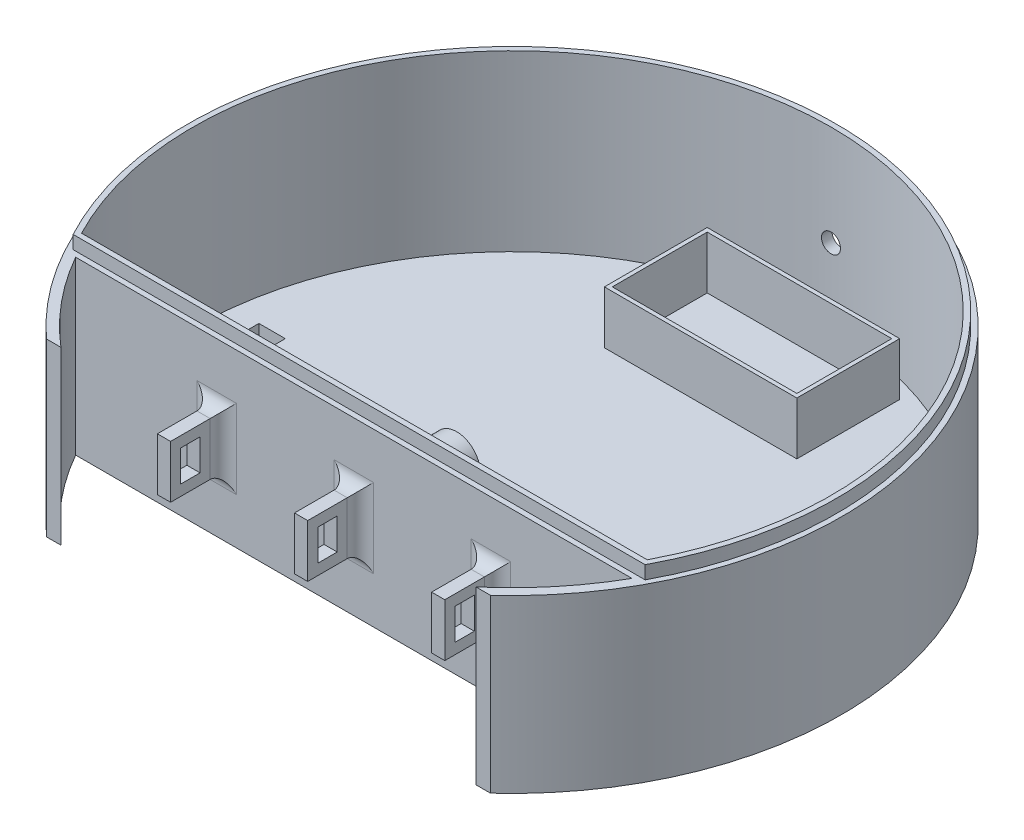
SolidWorks part; units mm, degrees
ref_plane "Plano frontal" through (0, 0, 0) normal (0, 0, 1) x (1, 0, 0)
ref_plane "Plano superior" through (0, 0, 0) normal (0, 1, 0) x (1, 0, 0)
ref_plane "Plano direito" through (0, 0, 0) normal (1, 0, 0) x (0, 0, -1)
sketch "Esboço1" plane through (0, 0, 0) normal (0, 1, 0) x (1, 0, 0)
  line L0 (-109.6586, -60) -> (109.6586, -60)
  circle A0 centre (0, 0) radius 125
  point P5 (0, -125)
  dimension "D1" = 250
  dimension "D2" = 65
extrude "Ressalto-extrusão1" add sketch "Esboço1" along normal blind 70 contours L0 A0 region at (0, 0, -22.5722)
sketch "Esboço5" plane through (0, 70, 0) normal (0, 1, 0) x (1, 0, 0)
  line L1 (-84.2002, -92.3868) -> (-78.7002, -92.3868)
  line L2 (-109.6586, -60) -> (109.6586, -60) construction
  line L3 (78.7002, -92.3868) -> (84.2002, -92.3868)
  line L4 (105.4943, -60) -> (109.6586, -60)
  line L5 (-109.6586, -60) -> (-105.4943, -60)
  arc A0 (-109.6586, -60) -> (-84.2002, -92.3868) centre (0, 0) ccw
  arc A1 (109.6586, -60) -> (84.2002, -92.3868) centre (0, 0) cw
  arc A2 (-105.4943, -60) -> (-78.7002, -92.3868) centre (0, 0) ccw
  arc A3 (78.7002, -92.3868) -> (105.4943, -60) centre (0, 0) ccw
  dimension "D1" = 5.5
  dimension "D2" = 5.5
extrude "Ressalto-extrusão4" add sketch "Esboço5" against normal up to surface (70 mm away) contours A2 L1 A0 L5 | A1 L3 A3 L4 up to face at (0, 0, -32.5)
shell "Casca1" thickness 4 removed face at (0, 70, 45.7497)
sketch "Esboço17" plane through (0, 4, 0) normal (0, 1, 0) x (1, 0, 0)
  line L0 (0, 0) -> (-50000, 0) construction
  line L1 (0, 0) -> (0, 50000) construction
  line L2 (-110, -14) -> (-100, -14)
  line L3 (-110, -14) -> (-110, 14)
  line L4 (-110, 14) -> (-100, 14)
  line L5 (-100, -14) -> (-100, 14)
  line L6 (-110, -14) -> (-100, 14) construction
  line L7 (-110, 14) -> (-100, -14) construction
  line L8 (110, 14) -> (100, -14) construction
  line L9 (110, -14) -> (100, 14) construction
  line L10 (100, -14) -> (100, 14)
  line L11 (110, 14) -> (100, 14)
  line L12 (110, -14) -> (110, 14)
  line L13 (110, -14) -> (100, -14)
  point P3 (-105, 0)
  point P15 (105, 0)
  dimension "D3" = 100
  dimension "D1" = 10
  dimension "D2" = 28
extrude "Corte-extrusão2" cut sketch "Esboço17" against normal blind 10
sketch "Esboço23" plane through (0, 70, 0) normal (0, 1, 0) x (1, 0, 0)
  line L7 (-108.4666, -58) -> (108.4666, -58)
  line L8 (-108.4666, -58) -> (108.4666, -58)
  arc A7 (108.4666, -58) -> (-108.4666, -58) centre (0, 0) ccw
  arc A8 (108.4666, -58) -> (-108.4666, -58) centre (0, 0) ccw
  dimension "D1" = 2
extrude "Corte-extrusão6" cut sketch "Esboço23" along normal blind 4 and the other way blind 5 flip side to cut
sketch "Esboço24" plane through (0, 4, 0) normal (0, 1, 0) x (1, 0, 0)
  line L0 (0, 0) -> (0, 50000) construction
  line L1 (-36.5, 91.0087) -> (49963.5, 91.0087) construction
  line L2 (-36.5, 110.5087) -> (36.5, 110.5087)
  line L3 (-36.5, 110.5087) -> (-36.5, 71.5087)
  line L4 (-36.5, 71.5087) -> (36.5, 71.5087)
  line L5 (36.5, 110.5087) -> (36.5, 71.5087)
  line L7 (35, 109.0087) -> (-35, 109.0087)
  line L8 (35, 109.0087) -> (35, 73.0087)
  line L9 (35, 73.0087) -> (-35, 73.0087)
  line L10 (-35, 109.0087) -> (-35, 73.0087)
  line L11 (35, 109.0087) -> (-35, 73.0087) construction
  line L12 (35, 73.0087) -> (-35, 109.0087) construction
  point P4 (-36.5, 91.0087)
  point P9 (0, 91.0087)
  dimension "D1" = 73
  dimension "D2" = 39
  dimension "D3" = 36.5
  dimension "D4" = 36.5
  dimension "D5" = 70
  dimension "D6" = 36
sketch "Esboço27" plane through (0, 0, 60) normal (0, 0, 1) x (1, 0, 0)
  line L0 (0, 49935) -> (0, -49935) construction
  line L1 (-105.4943, 65) -> (105.4943, 65) construction
  line L2 (104.9883, 32.5) -> (-49895.0117, 32.5) construction
  line L3 (105.4943, 0) -> (105.4943, 65) construction
  line L4 (-26, 65) -> (-26, -49935) construction
  line L5 (-49.5, 22.5) -> (-54.5, 22.5)
  line L6 (-49.5, 22.5) -> (-49.5, 42.5)
  line L7 (-49.5, 42.5) -> (-54.5, 42.5)
  line L8 (-54.5, 22.5) -> (-54.5, 42.5)
  line L9 (-49.5, 22.5) -> (-54.5, 42.5) construction
  line L10 (-49.5, 42.5) -> (-54.5, 22.5) construction
  line L11 (26, 65) -> (26, -49935) construction
  line L12 (49.5, 42.5) -> (54.5, 22.5) construction
  line L13 (49.5, 22.5) -> (54.5, 42.5) construction
  line L14 (54.5, 22.5) -> (54.5, 42.5)
  line L15 (49.5, 42.5) -> (54.5, 42.5)
  line L16 (49.5, 22.5) -> (49.5, 42.5)
  line L17 (49.5, 22.5) -> (54.5, 22.5)
  line L18 (-2.5, 42.5) -> (2.5, 22.5) construction
  line L19 (-2.5, 22.5) -> (2.5, 42.5) construction
  line L20 (2.5, 22.5) -> (2.5, 42.5)
  line L21 (-2.5, 42.5) -> (2.5, 42.5)
  line L22 (-2.5, 22.5) -> (-2.5, 42.5)
  line L23 (-2.5, 22.5) -> (2.5, 22.5)
  point P4 (0, 65)
  point P9 (105.4943, 32.5)
  point P10 (-52, 32.5)
  point P23 (52, 32.5)
  point P28 (0, 32.5)
  dimension "D1" = 5
  dimension "D2" = 20
  dimension "D3" = 26
  dimension "D4" = 26
  dimension "D5" = 52
extrude "Ressalto-extrusão5" add sketch "Esboço27" along normal blind 20
fillet "Filete2" radius 5 12 edges at (52, 42.5, 60) (49.5, 32.5, 60) (52, 22.5, 60) (-52, 42.5, 60) (-54.5, 32.5, 60) (-52, 22.5, 60) (0, 22.5, 60) (-2.5, 32.5, 60) (0, 42.5, 60) (54.5, 32.5, 60) (2.5, 32.5, 60) (-49.5, 32.5, 60)
sketch "Esboço28" plane through (-49.5, 0, 0) normal (1, 0, 0) x (0, 0, -1)
  line L0 (-80, 22.5) -> (-65, 22.5) construction
  line L1 (-65, 22.5) -> (-65, 42.5) construction
  line L2 (-65, 42.5) -> (-80, 42.5) construction
  line L3 (-80, 42.5) -> (-80, 22.5) construction
  line L4 (-80, 22.5) -> (-65, 22.5) construction
  line L5 (-65, 22.5) -> (-65, 42.5) construction
  line L6 (-65, 42.5) -> (-80, 42.5) construction
  line L7 (-80, 42.5) -> (-80, 22.5) construction
  line L8 (-80, 22.5) -> (-65, 22.5)
  line L9 (-65, 22.5) -> (-65, 42.5)
  line L10 (-65, 42.5) -> (-80, 42.5)
  line L11 (-80, 42.5) -> (-80, 22.5)
  line L12 (-80, 22.5) -> (-65, 22.5)
  line L13 (-65, 22.5) -> (-65, 42.5)
  line L14 (-65, 42.5) -> (-80, 42.5)
  line L15 (-80, 42.5) -> (-80, 22.5)
  line L16 (-72.5, 42.5) -> (-72.5, -49957.5) construction
  line L17 (-75, 32.5) -> (49925, 32.5) construction
  line L18 (-80, 22.5) -> (-65, 22.5)
  line L19 (-68.816, 26.5773) -> (-76.184, 26.5773)
  line L20 (-68.816, 26.5773) -> (-68.816, 38.4227)
  line L21 (-68.816, 38.4227) -> (-76.184, 38.4227)
  line L22 (-76.184, 26.5773) -> (-76.184, 38.4227)
  line L23 (-68.816, 26.5773) -> (-76.184, 38.4227) construction
  line L24 (-68.816, 38.4227) -> (-76.184, 26.5773) construction
  line L25 (-65, 22.5) -> (-65, 42.5)
  line L26 (-65, 42.5) -> (-80, 42.5)
  line L27 (-80, 42.5) -> (-80, 22.5)
  line L28 (-80, 22.5) -> (-65, 22.5)
  line L29 (-65, 22.5) -> (-65, 42.5)
  line L30 (-65, 42.5) -> (-80, 42.5)
  line L31 (-80, 42.5) -> (-80, 22.5)
  point P6 (-72.5, 42.5)
  point P9 (-80, 32.5)
  point P10 (-72.5, 32.5)
  point P11 (-72.5, 32.5)
extrude "Corte-extrusão7" cut sketch "Esboço28" against normal blind 5 and the other way blind 104 contours L22 L19 L20 L21 region at (-49.5, 32.5, 72.5)
sketch "Esboço32" plane through (0, 0, 56) normal (0, 0, -1) x (-1, 0, 0)
  line L0 (0, 0) -> (0, 50000) construction
  line L2 (-105.0373, 31.9328) -> (49894.9627, 31.9328) construction
  circle A0 centre (0, 31.9328) radius 3.6
  circle A1 centre (0, 31.9328) radius 9
extrude "Corte-extrusão8" cut sketch "Esboço32" along normal blind 187 contours A0
extrude "Ressalto-extrusão6" add sketch "Esboço32<3>" along normal blind 35
sketch "Esboço32<3>" plane through (0, 0, 56) normal (0, 0, -1) x (-1, 0, 0) same geometry as "Esboço32"
extrude "Ressalto-extrusão7" add sketch "Esboço32<4>" along normal blind 6 contours A0
sketch "Esboço32<4>" plane through (0, 0, 56) normal (0, 0, -1) x (-1, 0, 0) same geometry as "Esboço32"
fillet "Filete3" radius 10 1 edges at (-9, 31.9328, 56)
extrude "Ressalto-extrusão8" add sketch "Esboço24" along normal blind 20
sketch "Esboço33" plane through (0, 4, 0) normal (0, 1, 0) x (1, 0, 0)
  line L0 (-100, -14) -> (-100, 14) construction
  line L2 (64, -48) -> (4, -48)
  line L3 (64, -48) -> (64, 32)
  line L4 (64, 32) -> (4, 32)
  line L5 (4, -48) -> (4, 32)
  line L8 (-4, -48) -> (-64, -48)
  line L9 (-4, -48) -> (-4, 42)
  line L10 (-4, 42) -> (-64, 42)
  line L11 (-64, -48) -> (-64, 42)
  line L14 (-107.2614, -56) -> (107.2614, -56) construction
  line L15 (100, 14) -> (100, -14) construction
  line L20 (5, 35.3125) -> (65, -45.3125) construction
  line L21 (5, -45.3125) -> (65, 35.3125) construction
  line L26 (-4, 45) -> (-64, -45) construction
  line L27 (-4, -45) -> (-64, 45) construction
  point P0 (35, -5)
  point P9 (-34, 0)
  point P14 (100, 0)
  point P15 (35, -5)
  point P22 (-34, 0)
  dimension "D1" = 8
  dimension "D2" = 36
  dimension "D3" = 60
  dimension "D4" = 60
  dimension "D5" = 90
  dimension "D6" = 36
  dimension "D7" = 80
  dimension "D8" = 8
